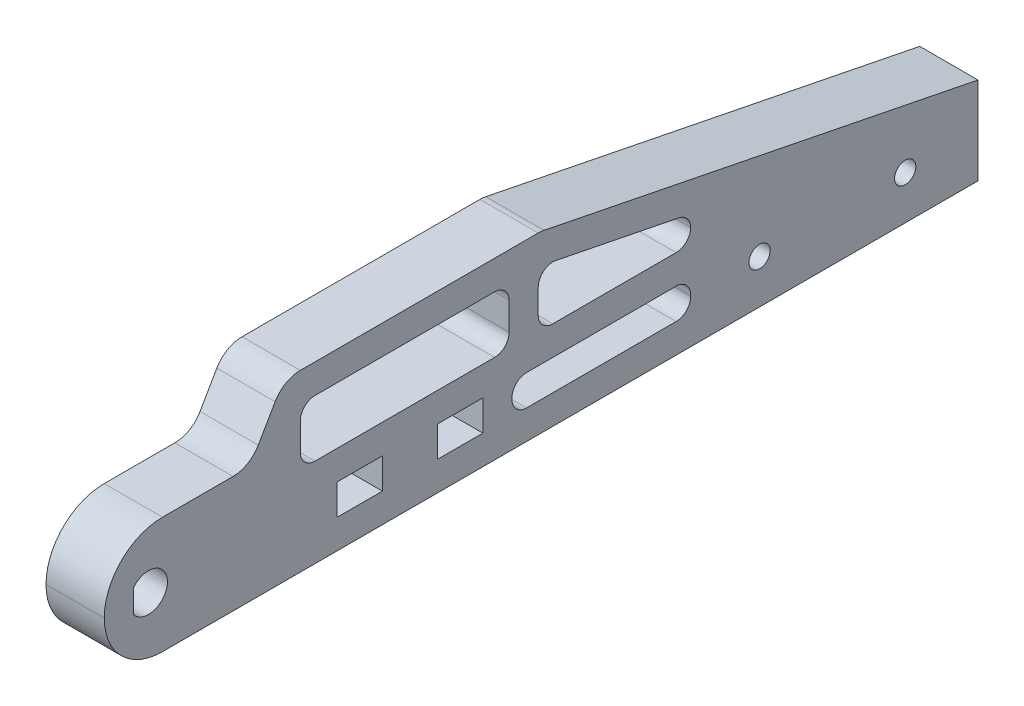
SolidWorks part; units mm, degrees
ref_plane "Front Plane" through (0, 0, 0) normal (0, 0, 1) x (1, 0, 0)
ref_plane "Top Plane" through (0, 0, 0) normal (0, 1, 0) x (1, 0, 0)
ref_plane "Right Plane" through (0, 0, 0) normal (1, 0, 0) x (0, 0, -1)
ref_plane "Plane1" through (0, 0, 0) normal (1, 0, 0) x (0, 0, -1)
sketch "Sketch1" plane through (0, 0, 0) normal (1, 0, 0) x (0, 0, -1)
  line L0 (0, 0) -> (150, 0)
  line L1 (150, 0) -> (150, 15)
  line L3 (150, 15) -> (75, 30)
  line L7 (25, 20) -> (30.7735, 30)
  line L8 (30.7735, 30) -> (75, 30)
  line L9 (0, 0) -> (0, 20)
  line L10 (0, 20) -> (25, 20)
  dimension "D1" = 150
  dimension "D2" = 15
  dimension "D3" = 75
  dimension "D5" = 25
  dimension "D6" = 20
  dimension "D7" = 10
  dimension "D8" = 120
extrude "Boss-Extrude1" add sketch "Sketch1" against normal blind 10
sketch "Sketch2" plane through (0, 0, 0) normal (1, 0, 0) x (0, 0, -1)
  line L20 (5, 11.9649) -> (5, 8.0351)
  line L23 (10.85, 19.5521) -> (10.85, 10.3168) construction
  line L26 (0, 20) -> (0, 0) construction
  arc A0 (5, 8.0351) -> (5, 11.9649) centre (7.595, 10) ccw
  point P0 (0, 10)
  dimension "D12" = 6.51
  dimension "D3" = 5
  dimension "D24" = 5.85
extrude "Cut-Extrude2" cut sketch "Sketch2" against normal through all
fillet "Fillet1" radius 10 2 edges at (-5, 0, 0) (-5, 20, 0)
fillet "Fillet2" radius 5 2 edges at (-5, 30, -75) (-5, 30, -30.7735)
sketch "Sketch5" plane through (0, 0, 0) normal (1, 0, 0) x (0, 0, -1)
  line L1 (135, 5) -> (140, 5)
  line L2 (135, 5) -> (135, 10)
  line L3 (135, 10) -> (140, 10)
  line L4 (140, 5) -> (140, 10)
  line L5 (135, 5) -> (140, 10) construction
  line L6 (135, 10) -> (140, 5) construction
  line L7 (110, 5) -> (115, 5)
  line L8 (110, 5) -> (110, 10)
  line L9 (110, 10) -> (115, 10)
  line L10 (115, 5) -> (115, 10)
  line L11 (110, 5) -> (115, 10) construction
  line L12 (110, 10) -> (115, 5) construction
  line L13 (150, 0) -> (150, 15) construction
  point P0 (137.5, 7.5)
  point P5 (112.5, 7.5)
  point P12 (150, 7.5)
  point P13 (140, 7.5)
  dimension "D1" = 5
  dimension "D2" = 5
  dimension "D3" = 10
  dimension "D4" = 20
  dimension "D5" = 5
  dimension "D6" = 5
extrude "Cut-Extrude5" [suppressed] cut sketch "Sketch5" against normal through all both and the other way through all
sketch "Sketch3" plane through (0, 0, 0) normal (1, 0, 0) x (0, 0, -1)
  line L6 (57.25, 5) -> (65, 5)
  line L11 (57.25, 5) -> (57.25, 10.25)
  line L12 (57.25, 10.25) -> (65, 10.25)
  line L17 (65, 5) -> (65, 10.25)
  line L19 (40, 10.25) -> (47.75, 10.25)
  line L20 (40, 10.25) -> (40, 5)
  line L21 (40, 5) -> (47.75, 5)
  line L22 (47.75, 10.25) -> (47.75, 5)
  line L23 (40, 10.25) -> (47.75, 5) construction
  line L24 (40, 5) -> (47.75, 10.25) construction
  line L29 (57.25, 5) -> (65, 10.25) construction
  line L30 (57.25, 10.25) -> (65, 5) construction
  line L48 (10, 0) -> (150, 0) construction
  point P0 (61.125, 7.625)
  point P15 (43.875, 7.625)
  dimension "D2" = 40
  dimension "D3" = 5.25
  dimension "D4" = 7.75
  dimension "D5" = 9.5
  dimension "D11" = 7.75
  dimension "D12" = 5.25
  dimension "D18" = 5
extrude "Cut-Extrude3" cut sketch "Sketch3" against normal through all both and the other way through all
sketch "Sketch6" plane through (0, 0, 0) normal (1, 0, 0) x (0, 0, -1)
  line L2 (150, 0) -> (150, 15) construction
  circle A0 centre (112.5, 7.5) radius 1.825
  circle A1 centre (137.5, 7.5) radius 1.825
  point P7 (150, 7.5)
  dimension "D1" = 3.65
  dimension "D2" = 3.65
  dimension "D3" = 12.5
  dimension "D4" = 25
extrude "Cut-Extrude6" cut sketch "Sketch6" against normal through all both and the other way through all
fillet "Fillet3" radius 5 1 edges at (-5, 20, -25)
sketch "Sketch7" plane through (0, 0, 0) normal (1, 0, 0) x (0, 0, -1)
  line L2 (69.5049, 25) -> (33.6603, 25)
  line L3 (33.6603, 25) -> (33.6603, 15.25)
  line L4 (70, 10.25) -> (100.675, 10.25)
  line L5 (100.675, 10.25) -> (100.675, 5)
  line L6 (100.675, 5) -> (70, 5)
  line L7 (70, 5) -> (70, 10.25)
  line L8 (10, 0) -> (150, 0) construction
  line L9 (65, 10.25) -> (65, 5) construction
  line L10 (100.675, 15.25) -> (100.675, 19.766)
  line L11 (74.5049, 30) -> (33.6603, 30) construction
  line L12 (100.675, 19.766) -> (74.5049, 25)
  line L13 (150, 15) -> (75.4855, 29.9029) construction
  line L14 (57.25, 10.25) -> (65, 10.25) construction
  line L15 (33.6603, 15.25) -> (69.5049, 15.25)
  line L16 (69.5049, 15.25) -> (69.5049, 25)
  line L17 (74.5049, 25) -> (74.5049, 15.25)
  line L18 (74.5049, 15.25) -> (100.675, 15.25)
  circle A0 centre (112.5, 7.5) radius 1.825 construction
  point P10 (100.675, 7.625)
  dimension "D1" = 5
  dimension "D2" = 5
  dimension "D3" = 11.825
  dimension "D4" = 5
  dimension "D5" = 5
  dimension "D6" = 5
  dimension "D7" = 5
extrude "Cut-Extrude7" cut sketch "Sketch7" against normal through all both and the other way through all
fillet "Fillet4" radius 2.5 12 edges at (-5, 5, -100.675) (-5, 10.25, -100.675) (-5, 10.25, -70) (-5, 5, -70) (-5, 15.25, -33.6603) (-5, 15.25, -69.5049) (-5, 25, -69.5049) (-5, 25, -33.6603) (-5, 15.25, -74.5049) (-5, 15.25, -100.675) (-5, 19.766, -100.675) (-5, 25, -74.5049)
